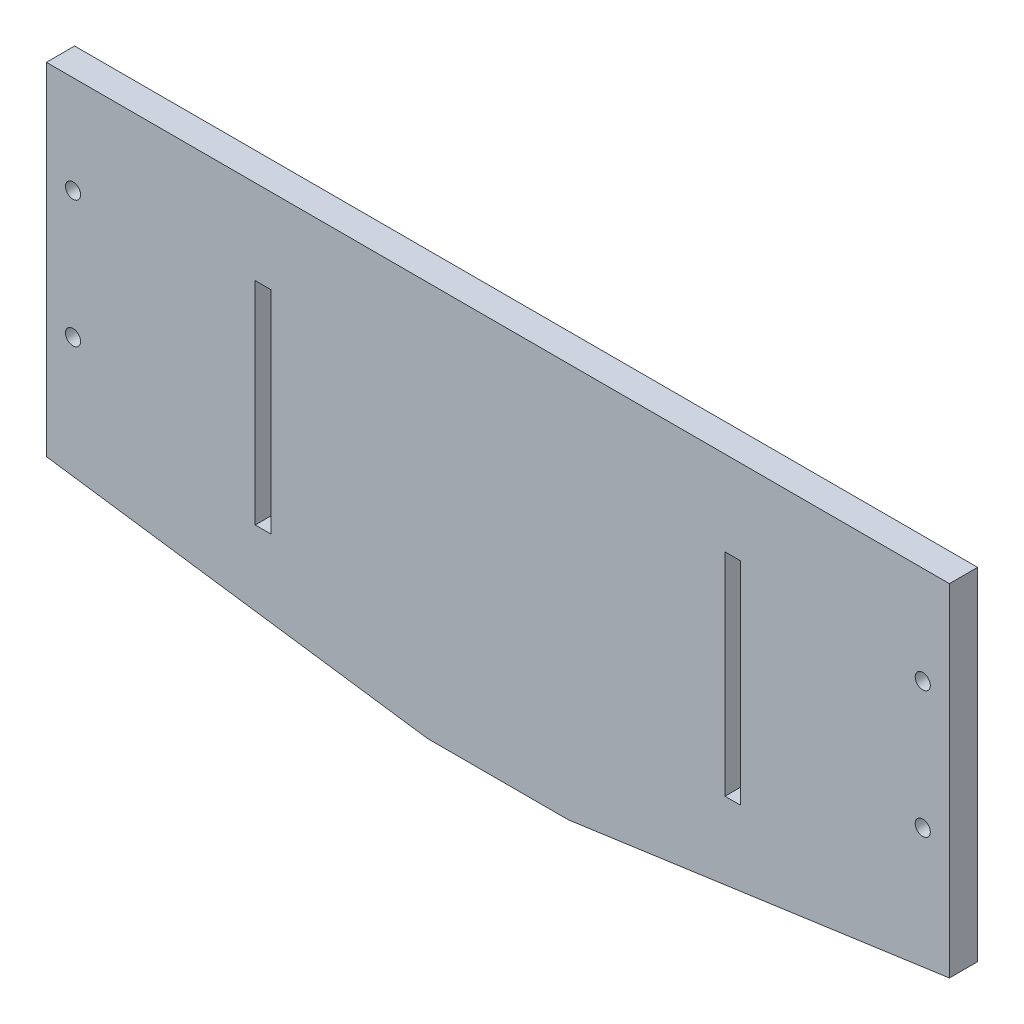
SolidWorks part; units mm, degrees
material "Acrylic (Medium-high impact)"
ref_plane "Front Plane" through (0, 0, 0) normal (0, 0, 1) x (1, 0, 0)
ref_plane "Top Plane" through (0, 0, 0) normal (0, 1, 0) x (1, 0, 0)
ref_plane "Right Plane" through (0, 0, 0) normal (1, 0, 0) x (0, 0, -1)
sketch "Sketch1" plane through (0, 0, 0) normal (0, 0, 1) x (1, 0, 0)
  line L1 (203.2, 127) -> (0, 127)
  line L2 (203.2, 127) -> (203.2, 0)
  line L3 (203.2, 0) -> (0, 0)
  line L4 (0, 127) -> (0, 0)
  line L5 (203.2, 127) -> (0, 0) construction
  line L6 (203.2, 0) -> (0, 127) construction
  point P0 (101.6, 63.5)
  dimension "D1" = 127
  dimension "D2" = 203.2
extrude "Boss-Extrude1" add sketch "Sketch1" along normal blind 6.35
hole_wizard "M3 Clearance Hole1" positions "Sketch2" profile "Sketch3" hole size "M3" standard "ANSI Metric" end condition through all
sketch "Sketch2" plane through (0, 0, 6.35) normal (0, 0, 1) x (1, 0, 0)
  line L0 (0, 127) -> (0, 0) construction
  line L1 (203.2, 127) -> (0, 127) construction
  line L2 (203.2, 0) -> (203.2, 127) construction
  point P0 (5.9944, 105.0036)
  point P2 (5.9944, 76.4286)
  point P4 (197.2056, 76.4286)
  point P6 (197.2056, 105.0036)
  dimension "D1" = 5.9944
  dimension "D2" = 21.9964
  dimension "D3" = 5.9944
  dimension "D4" = 28.575
sketch "Sketch3" plane through (5.9944, 105.0036, 6.35) normal (1, 0, 0) x (0, -1, 0)
  line L0 (0, 0) -> (0, 6.35)
  line L1 (0, 6.35) -> (1.7, 6.35)
  line L2 (1.7, 6.35) -> (1.7, 0)
  line L5 (1.7, 0) -> (0, 0)
  line L11 (0, -6.35) -> (0, 107.95) construction
  dimension "Thru Hole Dia." = 3.4
  dimension "Thru Hole Depth" = 6.35
sketch "Sketch4" plane through (0, 0, 6.35) normal (0, 0, 1) x (1, 0, 0)
  line L0 (0, 127) -> (0, 0) construction
  line L1 (46.99, 107.95) -> (50.4952, 107.95)
  line L2 (46.99, 107.95) -> (46.99, 60.325)
  line L3 (46.99, 60.325) -> (50.4952, 60.325)
  line L4 (50.4952, 107.95) -> (50.4952, 60.325)
  line L5 (152.7048, 107.95) -> (156.21, 107.95)
  line L6 (152.7048, 107.95) -> (152.7048, 60.325)
  line L7 (152.7048, 60.325) -> (156.21, 60.325)
  line L8 (156.21, 107.95) -> (156.21, 60.325)
  line L9 (203.2, 0) -> (203.2, 127) construction
  line L10 (203.2, 127) -> (0, 127) construction
  dimension "D1" = 3.5052
  dimension "D2" = 47.625
  dimension "D3" = 46.99
  dimension "D4" = 46.99
  dimension "D5" = 19.05
extrude "Cut-Extrude1" cut sketch "Sketch4" against normal through all
sketch "Sketch5" plane through (0, 0, 6.35) normal (0, 0, 1) x (1, 0, 0)
  line L0 (0, 50.1479) -> (85.725, 38.1)
  line L1 (0, 127) -> (0, 0) construction
  line L2 (85.725, 38.1) -> (117.475, 38.1)
  line L3 (117.475, 38.1) -> (203.2, 50.1479)
  line L4 (203.2, 0) -> (203.2, 127) construction
  line L5 (203.2, 50.1479) -> (203.2, 0)
  line L6 (203.2, 0) -> (0, 0)
  line L7 (0, 0) -> (0, 50.1479)
  dimension "D1" = 8
  dimension "D2" = 8
  dimension "D3" = 31.75
  dimension "D5" = 38.1
extrude "Cut-Extrude2" cut sketch "Sketch5" against normal through all
